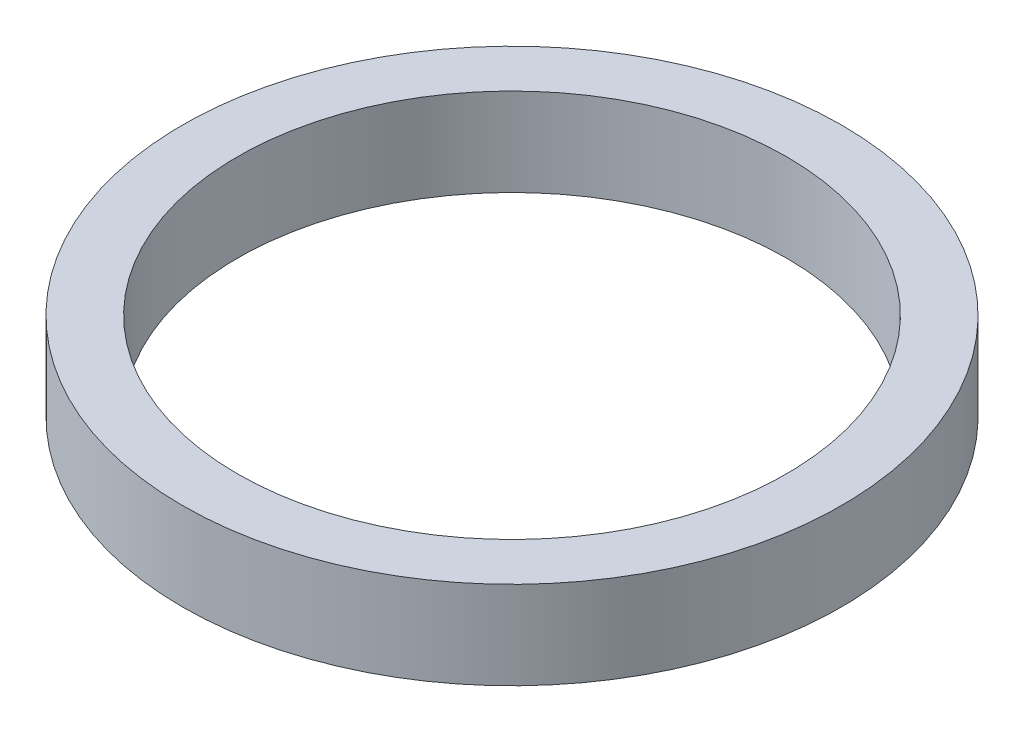
SolidWorks part; units mm, degrees
ref_plane "Front Plane" through (0, 0, 0) normal (0, 0, 1) x (1, 0, 0)
ref_plane "Top Plane" through (0, 0, 0) normal (0, 1, 0) x (1, 0, 0)
ref_plane "Right Plane" through (0, 0, 0) normal (1, 0, 0) x (0, 0, -1)
sketch "Sketch1" plane through (0, 0, 0) normal (0, 1, 0) x (1, 0, 0)
  circle A0 centre (0, 0) radius 60
  dimension "FLANGE_OD" = 120
extrude "Boss-Extrude1" add sketch "Sketch1" along normal blind 16
sketch "Sketch2" plane through (0, 0, 0) normal (0, 1, 0) x (1, 0, 0)
  circle A0 centre (0, 0) radius 50
  dimension "BORE_D" = 100
extrude "Cut-Extrude1" cut sketch "Sketch2" along normal through all
sketch "Sketch3" plane through (0, 16, 0) normal (0, 1, 0) x (1, 0, 0)
  circle A0 centre (0, 0) radius 26.7228 construction
  circle A1 centre (-26.7228, 0) radius 1.7934
  dimension "BOLT_D" = 3.5868
  dimension "BOLT_PCD" = 53.4457
extrude "Cut-Extrude2" cut sketch "Sketch3" against normal blind 9.9031 rebuild error yes
pattern_circular "CirPattern1" count 8 over 360 rebuild error yes
